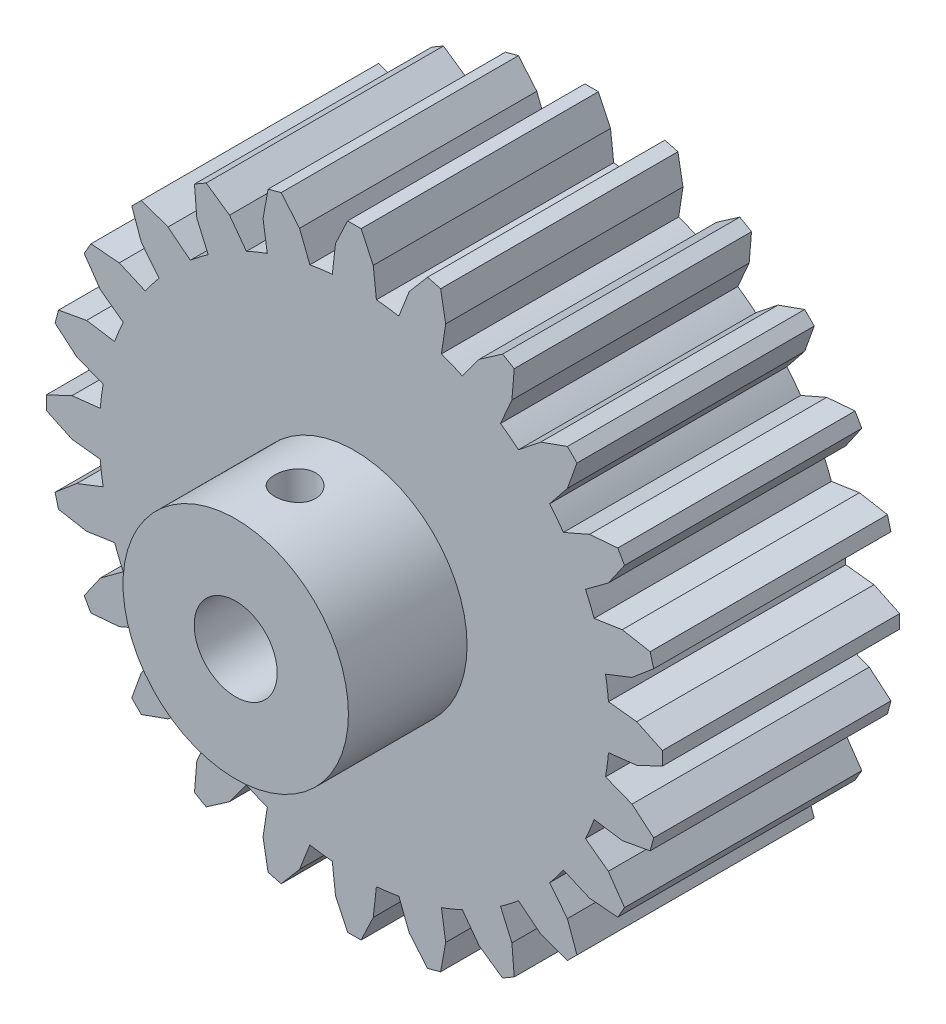
SolidWorks part; units mm, degrees
ref_plane "Plan de face" through (0, 0, 0) normal (0, 0, 1) x (1, 0, 0)
ref_plane "Plan de dessus" through (0, 0, 0) normal (0, 1, 0) x (1, 0, 0)
ref_plane "Plan de droite" through (0, 0, 0) normal (1, 0, 0) x (0, 0, -1)
sketch "Esquisse1" plane through (0, 0, 0) normal (0, 0, 1) x (1, 0, 0)
  line L0 (-1.8585, 21.4195) -> (-1.5915, 23.7996)
  line L1 (0, 2.2889) -> (0, 19223.5431) construction
  line L2 (-1.5915, 23.7996) -> (-0.5695, 25.9656)
  line L3 (-0.5695, 25.9656) -> (0.5695, 25.9656)
  line L4 (0, 0) -> (50000, 0) construction
  line L5 (1.8585, 21.4195) -> (1.5915, 23.7996)
  line L6 (1.5915, 23.7996) -> (0.5695, 25.9656)
  line L7 (3.7486, 21.1707) -> (4.6225, 23.4006)
  line L8 (4.6225, 23.4006) -> (6.1703, 25.2282)
  line L9 (7.6971, 22.5767) -> (7.2705, 24.9334)
  line L10 (7.339, 20.2087) -> (7.6971, 22.5767)
  line L11 (6.1703, 25.2282) -> (7.2705, 24.9334)
  line L12 (9.1003, 19.4791) -> (10.5215, 21.4068)
  line L13 (10.5215, 21.4068) -> (12.4896, 22.7716)
  line L14 (13.2781, 19.8153) -> (13.476, 22.2021)
  line L15 (12.3193, 17.6206) -> (13.2781, 19.8153)
  line L16 (12.4896, 22.7716) -> (13.476, 22.2021)
  line L17 (13.8317, 16.46) -> (15.7035, 17.9542)
  line L18 (15.7035, 17.9542) -> (17.9577, 18.7631)
  line L19 (17.9542, 15.7035) -> (18.7631, 17.9577)
  line L20 (16.46, 13.8317) -> (17.9542, 15.7035)
  line L21 (17.9577, 18.7631) -> (18.7631, 17.9577)
  line L22 (17.6206, 12.3193) -> (19.8153, 13.2781)
  line L23 (19.8153, 13.2781) -> (22.2021, 13.476)
  line L24 (21.4068, 10.5215) -> (22.7716, 12.4896)
  line L25 (19.4791, 9.1003) -> (21.4068, 10.5215)
  line L26 (22.2021, 13.476) -> (22.7716, 12.4896)
  line L27 (20.2087, 7.339) -> (22.5767, 7.6971)
  line L28 (22.5767, 7.6971) -> (24.9334, 7.2705)
  line L29 (23.4006, 4.6225) -> (25.2282, 6.1703)
  line L30 (21.1707, 3.7486) -> (23.4006, 4.6225)
  line L31 (24.9334, 7.2705) -> (25.2282, 6.1703)
  line L32 (21.4195, 1.8585) -> (23.7996, 1.5915)
  line L33 (23.7996, 1.5915) -> (25.9656, 0.5695)
  line L34 (23.7996, -1.5915) -> (25.9656, -0.5695)
  line L35 (21.4195, -1.8585) -> (23.7996, -1.5915)
  line L36 (25.9656, 0.5695) -> (25.9656, -0.5695)
  line L37 (21.1707, -3.7486) -> (23.4006, -4.6225)
  line L38 (23.4006, -4.6225) -> (25.2282, -6.1703)
  line L39 (22.5767, -7.6971) -> (24.9334, -7.2705)
  line L40 (20.2087, -7.339) -> (22.5767, -7.6971)
  line L41 (25.2282, -6.1703) -> (24.9334, -7.2705)
  line L42 (19.4791, -9.1003) -> (21.4068, -10.5215)
  line L43 (21.4068, -10.5215) -> (22.7716, -12.4896)
  line L44 (19.8153, -13.2781) -> (22.2021, -13.476)
  line L45 (17.6206, -12.3193) -> (19.8153, -13.2781)
  line L46 (22.7716, -12.4896) -> (22.2021, -13.476)
  line L47 (16.46, -13.8317) -> (17.9542, -15.7035)
  line L48 (17.9542, -15.7035) -> (18.7631, -17.9577)
  line L49 (15.7035, -17.9542) -> (17.9577, -18.7631)
  line L50 (13.8317, -16.46) -> (15.7035, -17.9542)
  line L51 (18.7631, -17.9577) -> (17.9577, -18.7631)
  line L52 (12.3193, -17.6206) -> (13.2781, -19.8153)
  line L53 (13.2781, -19.8153) -> (13.476, -22.2021)
  line L54 (10.5215, -21.4068) -> (12.4896, -22.7716)
  line L55 (9.1003, -19.4791) -> (10.5215, -21.4068)
  line L56 (13.476, -22.2021) -> (12.4896, -22.7716)
  line L57 (7.339, -20.2087) -> (7.6971, -22.5767)
  line L58 (7.6971, -22.5767) -> (7.2705, -24.9334)
  line L59 (4.6225, -23.4006) -> (6.1703, -25.2282)
  line L60 (3.7486, -21.1707) -> (4.6225, -23.4006)
  line L61 (7.2705, -24.9334) -> (6.1703, -25.2282)
  line L62 (1.8585, -21.4195) -> (1.5915, -23.7996)
  line L63 (1.5915, -23.7996) -> (0.5695, -25.9656)
  line L64 (-1.5915, -23.7996) -> (-0.5695, -25.9656)
  line L65 (-1.8585, -21.4195) -> (-1.5915, -23.7996)
  line L66 (0.5695, -25.9656) -> (-0.5695, -25.9656)
  line L67 (-3.7486, -21.1707) -> (-4.6225, -23.4006)
  line L68 (-4.6225, -23.4006) -> (-6.1703, -25.2282)
  line L69 (-7.6971, -22.5767) -> (-7.2705, -24.9334)
  line L70 (-7.339, -20.2087) -> (-7.6971, -22.5767)
  line L71 (-6.1703, -25.2282) -> (-7.2705, -24.9334)
  line L72 (-9.1003, -19.4791) -> (-10.5215, -21.4068)
  line L73 (-10.5215, -21.4068) -> (-12.4896, -22.7716)
  line L74 (-13.2781, -19.8153) -> (-13.476, -22.2021)
  line L75 (-12.3193, -17.6206) -> (-13.2781, -19.8153)
  line L76 (-12.4896, -22.7716) -> (-13.476, -22.2021)
  line L77 (-13.8317, -16.46) -> (-15.7035, -17.9542)
  line L78 (-15.7035, -17.9542) -> (-17.9577, -18.7631)
  line L79 (-17.9542, -15.7035) -> (-18.7631, -17.9577)
  line L80 (-16.46, -13.8317) -> (-17.9542, -15.7035)
  line L81 (-17.9577, -18.7631) -> (-18.7631, -17.9577)
  line L82 (-17.6206, -12.3193) -> (-19.8153, -13.2781)
  line L83 (-19.8153, -13.2781) -> (-22.2021, -13.476)
  line L84 (-21.4068, -10.5215) -> (-22.7716, -12.4896)
  line L85 (-19.4791, -9.1003) -> (-21.4068, -10.5215)
  line L86 (-22.2021, -13.476) -> (-22.7716, -12.4896)
  line L87 (-20.2087, -7.339) -> (-22.5767, -7.6971)
  line L88 (-22.5767, -7.6971) -> (-24.9334, -7.2705)
  line L89 (-23.4006, -4.6225) -> (-25.2282, -6.1703)
  line L90 (-21.1707, -3.7486) -> (-23.4006, -4.6225)
  line L91 (-24.9334, -7.2705) -> (-25.2282, -6.1703)
  line L92 (-21.4195, -1.8585) -> (-23.7996, -1.5915)
  line L93 (-23.7996, -1.5915) -> (-25.9656, -0.5695)
  line L94 (-23.7996, 1.5915) -> (-25.9656, 0.5695)
  line L95 (-21.4195, 1.8585) -> (-23.7996, 1.5915)
  line L96 (-25.9656, -0.5695) -> (-25.9656, 0.5695)
  line L97 (-21.1707, 3.7486) -> (-23.4006, 4.6225)
  line L98 (-23.4006, 4.6225) -> (-25.2282, 6.1703)
  line L99 (-22.5767, 7.6971) -> (-24.9334, 7.2705)
  line L100 (-20.2087, 7.339) -> (-22.5767, 7.6971)
  line L101 (-25.2282, 6.1703) -> (-24.9334, 7.2705)
  line L102 (-19.4791, 9.1003) -> (-21.4068, 10.5215)
  line L103 (-21.4068, 10.5215) -> (-22.7716, 12.4896)
  line L104 (-19.8153, 13.2781) -> (-22.2021, 13.476)
  line L105 (-17.6206, 12.3193) -> (-19.8153, 13.2781)
  line L106 (-22.7716, 12.4896) -> (-22.2021, 13.476)
  line L107 (-16.46, 13.8317) -> (-17.9542, 15.7035)
  line L108 (-17.9542, 15.7035) -> (-18.7631, 17.9577)
  line L109 (-15.7035, 17.9542) -> (-17.9577, 18.7631)
  line L110 (-13.8317, 16.46) -> (-15.7035, 17.9542)
  line L111 (-18.7631, 17.9577) -> (-17.9577, 18.7631)
  line L112 (-12.3193, 17.6206) -> (-13.2781, 19.8153)
  line L113 (-13.2781, 19.8153) -> (-13.476, 22.2021)
  line L114 (-10.5215, 21.4068) -> (-12.4896, 22.7716)
  line L115 (-9.1003, 19.4791) -> (-10.5215, 21.4068)
  line L116 (-13.476, 22.2021) -> (-12.4896, 22.7716)
  line L117 (-7.339, 20.2087) -> (-7.6971, 22.5767)
  line L118 (-7.6971, 22.5767) -> (-7.2705, 24.9334)
  line L119 (-4.6225, 23.4006) -> (-6.1703, 25.2282)
  line L120 (-3.7486, 21.1707) -> (-4.6225, 23.4006)
  line L121 (-7.2705, 24.9334) -> (-6.1703, 25.2282)
  arc A0 (-7.339, 20.2087) -> (-9.1003, 19.4791) centre (0, 0) ccw
  circle A1 centre (0, 0) radius 3.5
  arc A2 (-1.8585, 21.4195) -> (-3.7486, 21.1707) centre (0, 0) ccw
  arc A3 (3.7486, 21.1707) -> (1.8585, 21.4195) centre (0, 0) ccw
  arc A4 (9.1003, 19.4791) -> (7.339, 20.2087) centre (0, 0) ccw
  arc A5 (13.8317, 16.46) -> (12.3193, 17.6206) centre (0, 0) ccw
  arc A6 (17.6206, 12.3193) -> (16.46, 13.8317) centre (0, 0) ccw
  arc A7 (20.2087, 7.339) -> (19.4791, 9.1003) centre (0, 0) ccw
  arc A8 (21.4195, 1.8585) -> (21.1707, 3.7486) centre (0, 0) ccw
  arc A9 (21.1707, -3.7486) -> (21.4195, -1.8585) centre (0, 0) ccw
  arc A10 (19.4791, -9.1003) -> (20.2087, -7.339) centre (0, 0) ccw
  arc A11 (16.46, -13.8317) -> (17.6206, -12.3193) centre (0, 0) ccw
  arc A12 (12.3193, -17.6206) -> (13.8317, -16.46) centre (0, 0) ccw
  arc A13 (7.339, -20.2087) -> (9.1003, -19.4791) centre (0, 0) ccw
  arc A14 (1.8585, -21.4195) -> (3.7486, -21.1707) centre (0, 0) ccw
  arc A15 (-3.7486, -21.1707) -> (-1.8585, -21.4195) centre (0, 0) ccw
  arc A16 (-9.1003, -19.4791) -> (-7.339, -20.2087) centre (0, 0) ccw
  arc A17 (-13.8317, -16.46) -> (-12.3193, -17.6206) centre (0, 0) ccw
  arc A18 (-17.6206, -12.3193) -> (-16.46, -13.8317) centre (0, 0) ccw
  arc A19 (-20.2087, -7.339) -> (-19.4791, -9.1003) centre (0, 0) ccw
  arc A20 (-21.4195, -1.8585) -> (-21.1707, -3.7486) centre (0, 0) ccw
  arc A21 (-21.1707, 3.7486) -> (-21.4195, 1.8585) centre (0, 0) ccw
  arc A22 (-19.4791, 9.1003) -> (-20.2087, 7.339) centre (0, 0) ccw
  arc A23 (-16.46, 13.8317) -> (-17.6206, 12.3193) centre (0, 0) ccw
  arc A24 (-12.3193, 17.6206) -> (-13.8317, 16.46) centre (0, 0) ccw
  point P17 (0, 25.9656)
  point P156 (0, 0)
  dimension "D1" = 43
  dimension "D2" = 7
  dimension "D3" = 2.395
  dimension "D4" = 83.6
  dimension "D5" = 1.8585
  dimension "D6" = 2.395
  dimension "D7" = 0.5695
  dimension "D8" = 24
extrude "Boss.-Extru.1" add sketch "Esquisse1" along normal blind 20
sketch "Esquisse2" plane through (0, 0, 20) normal (0, 0, 1) x (1, 0, 0)
  circle A0 centre (0, 0) radius 3.5
  circle A1 centre (0, 0) radius 9.5
  circle A2 centre (0, 0) radius 3.5 construction
  dimension "D1" = 6
extrude "Boss.-Extru.2" add sketch "Esquisse2" along normal blind 10
sketch "Esquisse3" plane through (0, 0, 0) normal (0, 1, 0) x (1, 0, 0)
  line L0 (-7.5, -25) -> (49992.5, -25) construction
  line L1 (-9.5, -20) -> (-9.5, -30) construction
  line L2 (0, -30) -> (0, 49970) construction
  line L3 (-9.5, -30) -> (9.5, -30) construction
  circle A0 centre (0, -25) radius 1.725
  point P6 (-9.5, -25)
  point P7 (0, 0)
  point P8 (0, 0)
  point P13 (0, -30)
  dimension "D1" = 3.45
extrude "Enlèv. mat.-Extru.1" cut sketch "Esquisse3" along normal blind 10
